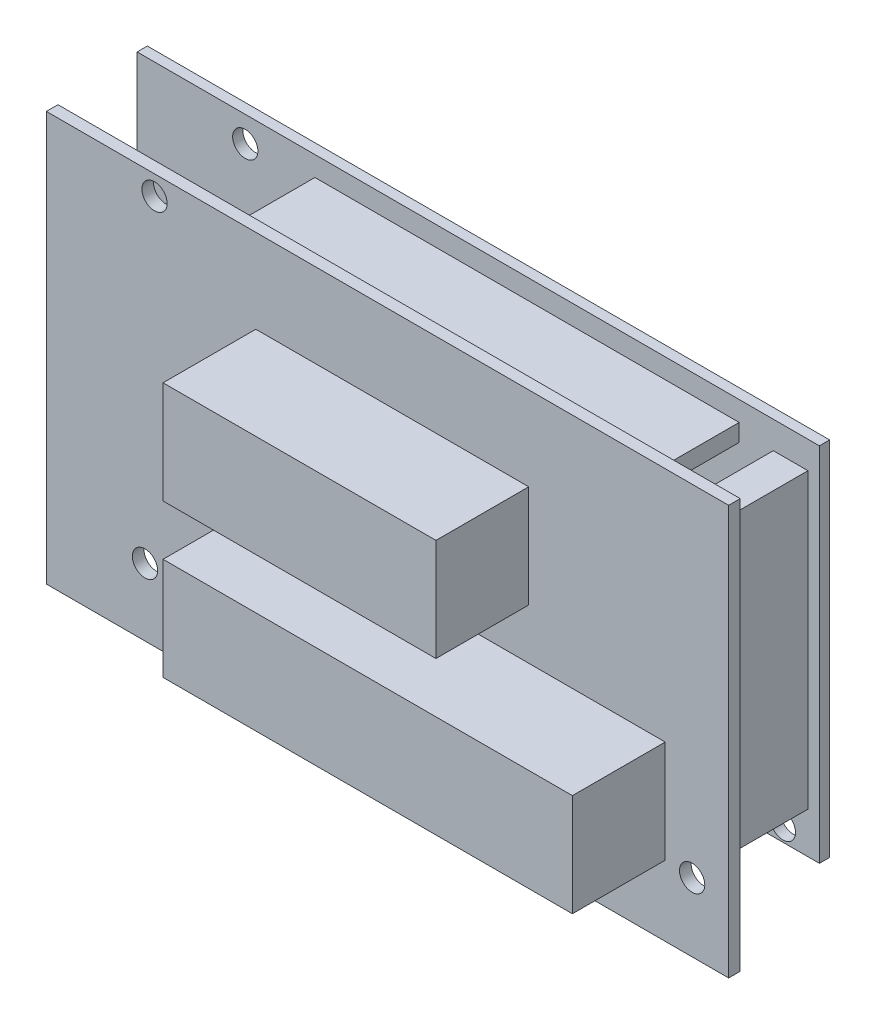
SolidWorks part; units mm, degrees
ref_plane "Plano frontal" through (0, 0, 0) normal (0, 0, 1) x (1, 0, 0)
ref_plane "Plano superior" through (0, 0, 0) normal (0, 1, 0) x (1, 0, 0)
ref_plane "Plano direito" through (0, 0, 0) normal (1, 0, 0) x (0, 0, -1)
sketch "Esboço1" plane through (0, 0, 0) normal (0, 0, 1) x (1, 0, 0)
  line L1 (-50, 30) -> (50, 30)
  line L2 (-50, 30) -> (-50, -30)
  line L3 (-50, -30) -> (50, -30)
  line L4 (50, 30) -> (50, -30)
  line L5 (-50, 30) -> (50, -30) construction
  line L6 (-50, -30) -> (50, 30) construction
  circle A0 centre (-34.15, 27.15) radius 1.85
  circle A1 centre (-35.55, -20.15) radius 1.85
  circle A2 centre (44.65, -19.95) radius 1.85
  point P0 (0, 0)
  dimension "D3" = 1
  dimension "D4" = 3.7
  dimension "D5" = 14
  dimension "D6" = 12.6
  dimension "D7" = 8
  dimension "D8" = 3.5
  dimension "D9" = 8.2
  dimension "D1" = 60
  dimension "D2" = 100
extrude "Ressalto-extrusão1" add sketch "Esboço1" along normal blind 1.7
sketch "Esboço2" plane through (0, 0, 1.7) normal (0, 0, 1) x (1, 0, 0)
  line L0 (-50, -30) -> (50, -30) construction
  line L1 (-19.3, -4.7) -> (40.7, -4.7)
  line L2 (-19.3, -4.7) -> (-19.3, -19.7)
  line L3 (-19.3, -19.7) -> (40.7, -19.7)
  line L4 (40.7, -4.7) -> (40.7, -19.7)
  line L5 (50, -30) -> (50, 30) construction
  line L7 (-19.3, 2.7) -> (20.7, 2.7)
  line L8 (-19.3, 2.7) -> (-19.3, 17.7)
  line L9 (-19.3, 17.7) -> (20.7, 17.7)
  line L10 (20.7, 2.7) -> (20.7, 17.7)
  dimension "D1" = 60
  dimension "D2" = 15
  dimension "D3" = 10.3
  dimension "D4" = 9.3
  dimension "D5" = 40
  dimension "D6" = 7.4
extrude "Ressalto-extrusão2" add sketch "Esboço2" along normal blind 13.6
sketch "Esboço3" plane through (0, 0, 0) normal (0, 0, -1) x (-1, 0, 0)
  line L0 (50, -30) -> (-50, -30) construction
  line L1 (50, 30.9) -> (-50, 30.9)
  line L2 (50, 30.9) -> (50, -22.1)
  line L3 (50, -22.1) -> (-50, -22.1)
  line L4 (-50, 30.9) -> (-50, -22.1)
  line L5 (50, 30) -> (50, -30) construction
  line L6 (-50, -30) -> (-50, 30) construction
  circle A0 centre (-44.65, -19.95) radius 1.85 construction
  circle A1 centre (34.15, 27.15) radius 1.85 construction
  circle A2 centre (35.55, -20.15) radius 1.85 construction
  circle A3 centre (-44.65, -19.95) radius 1.85
  circle A4 centre (34.15, 27.15) radius 1.85
  circle A5 centre (35.55, -20.15) radius 1.85
  dimension "D1" = 7.9
  dimension "D2" = 53
extrude "Ressalto-extrusão6" add sketch "Esboço3" along normal blind 1.5 from offset 11.6 separate body
sketch "Esboço4" plane through (0, 0, -11.6) normal (0, 0, 1) x (1, 0, 0)
  line L1 (-23.9415, 27.9898) -> (38.2426, 27.9898)
  line L2 (-23.9415, 27.9898) -> (-23.9415, 25.4498)
  line L3 (-23.9415, 25.4498) -> (38.2426, 25.4498)
  line L4 (38.2426, 27.9898) -> (38.2426, 25.4498)
  line L5 (48.3249, 26.9052) -> (43.2449, 26.9052)
  line L6 (48.3249, 26.9052) -> (48.3249, -16.0526)
  line L7 (48.3249, -16.0526) -> (43.2449, -16.0526)
  line L8 (43.2449, 26.9052) -> (43.2449, -16.0526)
  line L9 (38.2426, -19.9599) -> (-17.8292, -19.9599)
  line L10 (38.2426, -19.9599) -> (38.2426, -17.4199)
  line L11 (38.2426, -17.4199) -> (-17.8292, -17.4199)
  line L12 (-17.8292, -19.9599) -> (-17.8292, -17.4199)
  dimension "D1" = 2.54
  dimension "D2" = 5.08
extrude "Ressalto-extrusão8" add sketch "Esboço4" along normal up to surface (11.6 mm away) up to face at (0, 0, 0)
equation "\"D5@Esboço2\"=\"D1@Esboço2\"*2/3"
equation "\"D2@Esboço4\"=\"D1@Esboço4\"*2"
